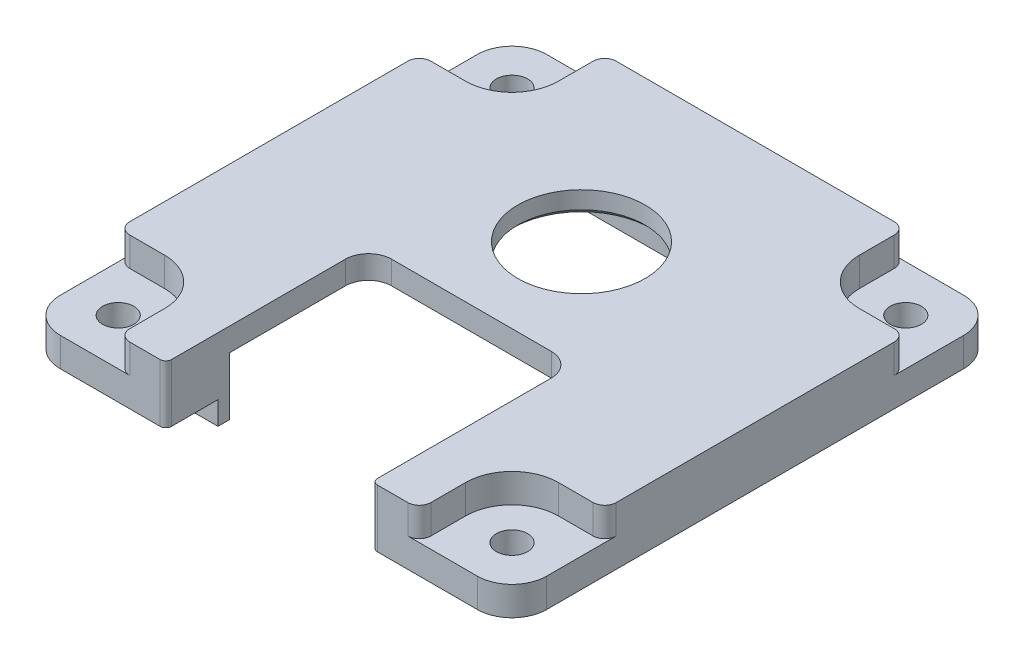
SolidWorks part; units mm, degrees
material "ABS"
ref_plane "Front Plane" through (0, 0, 0) normal (0, 0, 1) x (1, 0, 0)
ref_plane "Top Plane" through (0, 0, 0) normal (0, 1, 0) x (1, 0, 0)
ref_plane "Right Plane" through (0, 0, 0) normal (1, 0, 0) x (0, 0, -1)
sketch "Sketch2" plane through (0, 0, 0) normal (0, 1, 0) x (1, 0, 0)
  line L0 (0, 0) -> (0, 6) construction
  line L1 (-21, 21) -> (21, 21)
  line L2 (-21, 21) -> (-21, -21)
  line L3 (-21, -21) -> (21, -21)
  line L4 (21, 21) -> (21, -21)
  line L5 (-21, 21) -> (21, -21) construction
  line L6 (-21, -21) -> (21, 21) construction
  circle A0 centre (0, 6) radius 5.5
  point P0 (0, 0)
  dimension "D3" = 11
  dimension "D1" = 42
  dimension "D2" = 42
  dimension "D4" = 6
extrude "Boss-Extrude1" add sketch "Sketch2" against normal blind 2
ref_plane "Plane1" through (0, 0, -6) normal (0, 0, 1) x (1, 0, 0)
sketch "Sketch3" plane through (0, 0, -6) normal (0, 0, 1) x (1, 0, 0)
  line L1 (-5.5, 0) -> (-6.25, 0)
  line L2 (-6.25, 0) -> (-6.25, 3)
  line L4 (-6.25, 3) -> (-5.25, 3)
  line L8 (-5.5, 2) -> (-5.5, 0)
  line L9 (0, 0) -> (0, 7.3617) construction
  line L10 (-5.5, 2) -> (-4.5, 2.727)
  line L11 (-4.5, 2.727) -> (-5.25, 3)
  line L13 (0, 1.0892) -> (-5.25, 3) construction
  dimension "D1" = 70
  dimension "D2" = 3
  dimension "D3" = 1
  dimension "D4" = 0.75
  dimension "D5" = 0.75
  dimension "D6" = 2
revolve "Revolve1" [suppressed] add sketch "Sketch3" angle 360 about L9
sketch "Sketch4" plane through (0, -2, 0) normal (0, -1, 0) x (1, 0, 0)
  line L8 (-21, 21) -> (21, 21)
  line L9 (-21, 21) -> (-21, -21)
  line L10 (-21, -21) -> (21, -21)
  line L11 (21, 21) -> (21, -21)
  line L12 (-21, 21) -> (21, -21) construction
  line L13 (-21, -21) -> (21, 21) construction
  line L14 (-17, 11.5228) -> (-17, -11.5228)
  line L15 (-11.5228, -17) -> (11.5228, -17)
  line L16 (17, 11.5228) -> (17, -11.5228)
  line L17 (-11.5228, 17) -> (11.5228, 17)
  arc A12 (-16.5455, -12.0207) -> (-12.0207, -16.5455) centre (-17, -17) cw
  arc A13 (12.0207, -16.5455) -> (16.5455, -12.0207) centre (17, -17) cw
  arc A14 (16.5455, 12.0207) -> (12.0207, 16.5455) centre (17, 17) cw
  arc A15 (-12.0207, 16.5455) -> (-16.5455, 12.0207) centre (-17, 17) cw
  arc A16 (-16.5455, -12.0207) -> (-17, -11.5228) centre (-16.5, -11.5228) cw
  arc A17 (-12.0207, -16.5455) -> (-11.5228, -17) centre (-11.5228, -16.5) ccw
  arc A18 (12.0207, -16.5455) -> (11.5228, -17) centre (11.5228, -16.5) cw
  arc A19 (16.5455, -12.0207) -> (17, -11.5228) centre (16.5, -11.5228) ccw
  arc A20 (16.5455, 12.0207) -> (17, 11.5228) centre (16.5, 11.5228) cw
  arc A21 (12.0207, 16.5455) -> (11.5228, 17) centre (11.5228, 16.5) ccw
  arc A22 (-12.0207, 16.5455) -> (-11.5228, 17) centre (-11.5228, 16.5) cw
  arc A23 (-16.5455, 12.0207) -> (-17, 11.5228) centre (-16.5, 11.5228) ccw
  point P32 (0, 0)
extrude "Boss-Extrude2" add sketch "Sketch4" along normal blind 3
sketch "Sketch6" plane through (0, -2, 0) normal (0, -1, 0) x (1, 0, 0)
  line L8 (-16.5, 11.5228) -> (-16.5, -11.5228)
  line L9 (-11.5228, -16.5) -> (11.5228, -16.5)
  line L10 (16.5, -11.5228) -> (16.5, 11.5228)
  line L11 (11.5228, 16.5) -> (-11.5228, 16.5)
  line L12 (-16.5, 11.5228) -> (-16.5, -11.5228)
  line L13 (-11.5228, -16.5) -> (11.5228, -16.5)
  line L14 (16.5, -11.5228) -> (16.5, 11.5228)
  line L15 (11.5228, 16.5) -> (-11.5228, 16.5)
  line L16 (-17, 11.5228) -> (-17, -11.5228)
  line L17 (-11.5228, -17) -> (11.5228, -17)
  line L18 (17, -11.5228) -> (17, 11.5228)
  line L19 (11.5228, 17) -> (-11.5228, 17)
  line L20 (-17, 11.5228) -> (-17, -11.5228)
  line L21 (-11.5228, -17) -> (11.5228, -17)
  line L22 (17, -11.5228) -> (17, 11.5228)
  line L23 (11.5228, 17) -> (-11.5228, 17)
  arc A24 (-11.5228, -16.5) -> (-16.5, -11.5228) centre (-17, -17) ccw
  arc A25 (16.5, -11.5228) -> (11.5228, -16.5) centre (17, -17) ccw
  arc A26 (11.5228, 16.5) -> (16.5, 11.5228) centre (17, 17) ccw
  arc A27 (-16.5, 11.5228) -> (-11.5228, 16.5) centre (-17, 17) ccw
  arc A28 (-11.5228, -16.5) -> (-16.5, -11.5228) centre (-17, -17) ccw
  arc A29 (16.5, -11.5228) -> (11.5228, -16.5) centre (17, -17) ccw
  arc A30 (11.5228, 16.5) -> (16.5, 11.5228) centre (17, 17) ccw
  arc A31 (-16.5, 11.5228) -> (-11.5228, 16.5) centre (-17, 17) ccw
  arc A32 (-17, -11.5228) -> (-16.5455, -12.0207) centre (-16.5, -11.5228) ccw
  arc A33 (-12.0207, -16.5455) -> (-16.5455, -12.0207) centre (-17, -17) ccw
  arc A34 (-12.0207, -16.5455) -> (-11.5228, -17) centre (-11.5228, -16.5) ccw
  arc A35 (11.5228, -17) -> (12.0207, -16.5455) centre (11.5228, -16.5) ccw
  arc A36 (16.5455, -12.0207) -> (12.0207, -16.5455) centre (17, -17) ccw
  arc A37 (16.5455, -12.0207) -> (17, -11.5228) centre (16.5, -11.5228) ccw
  arc A38 (17, 11.5228) -> (16.5455, 12.0207) centre (16.5, 11.5228) ccw
  arc A39 (12.0207, 16.5455) -> (16.5455, 12.0207) centre (17, 17) ccw
  arc A40 (12.0207, 16.5455) -> (11.5228, 17) centre (11.5228, 16.5) ccw
  arc A41 (-11.5228, 17) -> (-12.0207, 16.5455) centre (-11.5228, 16.5) ccw
  arc A42 (-16.5455, 12.0207) -> (-12.0207, 16.5455) centre (-17, 17) ccw
  arc A43 (-16.5455, 12.0207) -> (-17, 11.5228) centre (-16.5, 11.5228) ccw
  arc A44 (-17, -11.5228) -> (-16.5455, -12.0207) centre (-16.5, -11.5228) ccw
  arc A45 (-12.0207, -16.5455) -> (-16.5455, -12.0207) centre (-17, -17) ccw
  arc A46 (-12.0207, -16.5455) -> (-11.5228, -17) centre (-11.5228, -16.5) ccw
  arc A47 (11.5228, -17) -> (12.0207, -16.5455) centre (11.5228, -16.5) ccw
  arc A48 (16.5455, -12.0207) -> (12.0207, -16.5455) centre (17, -17) ccw
  arc A49 (16.5455, -12.0207) -> (17, -11.5228) centre (16.5, -11.5228) ccw
  arc A50 (17, 11.5228) -> (16.5455, 12.0207) centre (16.5, 11.5228) ccw
  arc A51 (12.0207, 16.5455) -> (16.5455, 12.0207) centre (17, 17) ccw
  arc A52 (12.0207, 16.5455) -> (11.5228, 17) centre (11.5228, 16.5) ccw
  arc A53 (-11.5228, 17) -> (-12.0207, 16.5455) centre (-11.5228, 16.5) ccw
  arc A54 (-16.5455, 12.0207) -> (-12.0207, 16.5455) centre (-17, 17) ccw
  arc A55 (-16.5455, 12.0207) -> (-17, 11.5228) centre (-16.5, 11.5228) ccw
  dimension "D1" = 0.5
  dimension "D2" = 0
extrude "Boss-Extrude3" add sketch "Sketch6" along normal up to surface (3 mm away) up to face at (0, -5, 0)
sketch "Sketch7" plane through (0, -2, 0) normal (0, -1, 0) x (1, 0, 0)
  line L8 (10.6754, 15.5) -> (-10.6754, 15.5)
  line L9 (-15.5, 10.6754) -> (-15.5, -10.6754)
  line L10 (-10.6754, -15.5) -> (10.6754, -15.5)
  line L11 (15.5, -10.6754) -> (15.5, 10.6754)
  line L12 (10.6754, 15.5) -> (-10.6754, 15.5)
  line L13 (-15.5, 10.6754) -> (-15.5, -10.6754)
  line L14 (-10.6754, -15.5) -> (10.6754, -15.5)
  line L15 (15.5, -10.6754) -> (15.5, 10.6754)
  line L16 (11.5228, 16.5) -> (-11.5228, 16.5)
  line L17 (-16.5, 11.5228) -> (-16.5, -11.5228)
  line L18 (-11.5228, -16.5) -> (11.5228, -16.5)
  line L19 (16.5, -11.5228) -> (16.5, 11.5228)
  line L20 (11.5228, 16.5) -> (-11.5228, 16.5)
  line L21 (-16.5, 11.5228) -> (-16.5, -11.5228)
  line L22 (-11.5228, -16.5) -> (11.5228, -16.5)
  line L23 (16.5, -11.5228) -> (16.5, 11.5228)
  arc A8 (10.6754, 15.5) -> (15.5, 10.6754) centre (17, 17) ccw
  arc A9 (-15.5, 10.6754) -> (-10.6754, 15.5) centre (-17, 17) ccw
  arc A10 (-10.6754, -15.5) -> (-15.5, -10.6754) centre (-17, -17) ccw
  arc A11 (15.5, -10.6754) -> (10.6754, -15.5) centre (17, -17) ccw
  arc A12 (10.6754, 15.5) -> (15.5, 10.6754) centre (17, 17) ccw
  arc A13 (-15.5, 10.6754) -> (-10.6754, 15.5) centre (-17, 17) ccw
  arc A14 (-10.6754, -15.5) -> (-15.5, -10.6754) centre (-17, -17) ccw
  arc A15 (15.5, -10.6754) -> (10.6754, -15.5) centre (17, -17) ccw
  arc A16 (11.5228, 16.5) -> (16.5, 11.5228) centre (17, 17) ccw
  arc A17 (-16.5, 11.5228) -> (-11.5228, 16.5) centre (-17, 17) ccw
  arc A18 (-11.5228, -16.5) -> (-16.5, -11.5228) centre (-17, -17) ccw
  arc A19 (16.5, -11.5228) -> (11.5228, -16.5) centre (17, -17) ccw
  arc A20 (11.5228, 16.5) -> (16.5, 11.5228) centre (17, 17) ccw
  arc A21 (-16.5, 11.5228) -> (-11.5228, 16.5) centre (-17, 17) ccw
  arc A22 (-11.5228, -16.5) -> (-16.5, -11.5228) centre (-17, -17) ccw
  arc A23 (16.5, -11.5228) -> (11.5228, -16.5) centre (17, -17) ccw
  dimension "D1" = 1
  dimension "D2" = 0
extrude "Boss-Extrude5" add sketch "Sketch7" along normal blind 5
sketch "Sketch9" plane through (0, 0, 0) normal (0, 1, 0) x (1, 0, 0)
  circle A0 centre (-17, 17) radius 1.35
  circle A1 centre (17, 17) radius 1.35
  circle A2 centre (-17, -17) radius 1.35
  circle A3 centre (17, -17) radius 1.35
  dimension "D1" = 2.7
sketch "Sketch8" plane through (0, 0, 0) normal (0, 1, 0) x (1, 0, 0)
  line L0 (-17, 13) -> (-21, 13)
  line L1 (-21, -21) -> (-21, 21) construction
  line L2 (-21, 13) -> (-21, 21)
  line L3 (-13, 17) -> (-13, 21)
  line L4 (-21, 21) -> (21, 21) construction
  line L5 (-13, 21) -> (-21, 21)
  line L6 (13, 17) -> (13, 21)
  line L7 (13, 21) -> (21, 21)
  line L8 (21, 21) -> (21, 13)
  line L9 (17, 13) -> (21, 13)
  line L10 (21, -21) -> (21, 21) construction
  line L11 (-21, -17) -> (-21, -21)
  line L12 (-21, -21) -> (-17, -21)
  line L13 (-21, -21) -> (21, -21) construction
  line L14 (-13, -17) -> (-13, -21)
  line L15 (-13, -21) -> (-17, -21)
  line L16 (-17, -13) -> (-21, -13)
  line L17 (-21, -13) -> (-21, -17)
  line L18 (17, -13) -> (21, -13)
  line L19 (21, -13) -> (21, -21)
  line L20 (21, -21) -> (17, -21)
  line L21 (13, -17) -> (13, -21)
  line L22 (13, -21) -> (17, -21)
  arc A0 (-17, 13) -> (-13, 17) centre (-17, 17) ccw
  arc A2 (13, 17) -> (17, 13) centre (17, 17) ccw
  arc A3 (17, -13) -> (13, -17) centre (17, -17) ccw
  arc A4 (-13, -17) -> (-17, -13) centre (-17, -17) ccw
extrude "Cut-Extrude1" cut sketch "Sketch8" against normal blind 2.5
extrude "Cut-Extrude2" cut sketch "Sketch9" against normal through all
fillet "Fillet1" radius 3 4 edges at (21, -3.75, 21) (-21, -3.75, 21) (21, -3.75, -21) (-21, -3.75, -21)
fillet "Fillet2" radius 1 8 edges at (-21, -1.25, -13) (-13, -1.25, -21) (13, -1.25, -21) (21, -1.25, -13) (21, -1.25, 13) (13, -1.25, 21) (-13, -1.25, 21) (-21, -1.25, 13)
chamfer "Chamfer1" distance 0.5 angle 45 1 edges at (0, -2, -0.5)
sketch "Sketch11" plane through (0, 0, 0) normal (0, 1, 0) x (1, 0, 0)
  line L0 (-12, -21) -> (12, -21) construction
  line L1 (-8.89, -3.5) -> (8.89, -3.5)
  line L2 (-8.89, -3.5) -> (-8.89, -21)
  line L3 (-8.89, -21) -> (8.89, -21)
  line L4 (8.89, -3.5) -> (8.89, -21)
  line L5 (-8.89, -3.5) -> (8.89, -21) construction
  line L6 (-8.89, -21) -> (8.89, -3.5) construction
  point P0 (0, -12.25)
  point P7 (0, -21)
  point P8 (0, -21)
  dimension "D1" = 17.78
  dimension "D2" = 17.5
extrude "Cut-Extrude3" cut sketch "Sketch11" against normal up to surface (7 mm away) up to face at (0, -7, 0)
fillet "Fillet3" radius 2 2 edges at (8.89, -1, 3.5) (-8.89, -1, 3.5)
fillet "Fillet4" radius 0.5 2 edges at (8.89, -2.5, 21) (-8.89, -2.5, 21)
